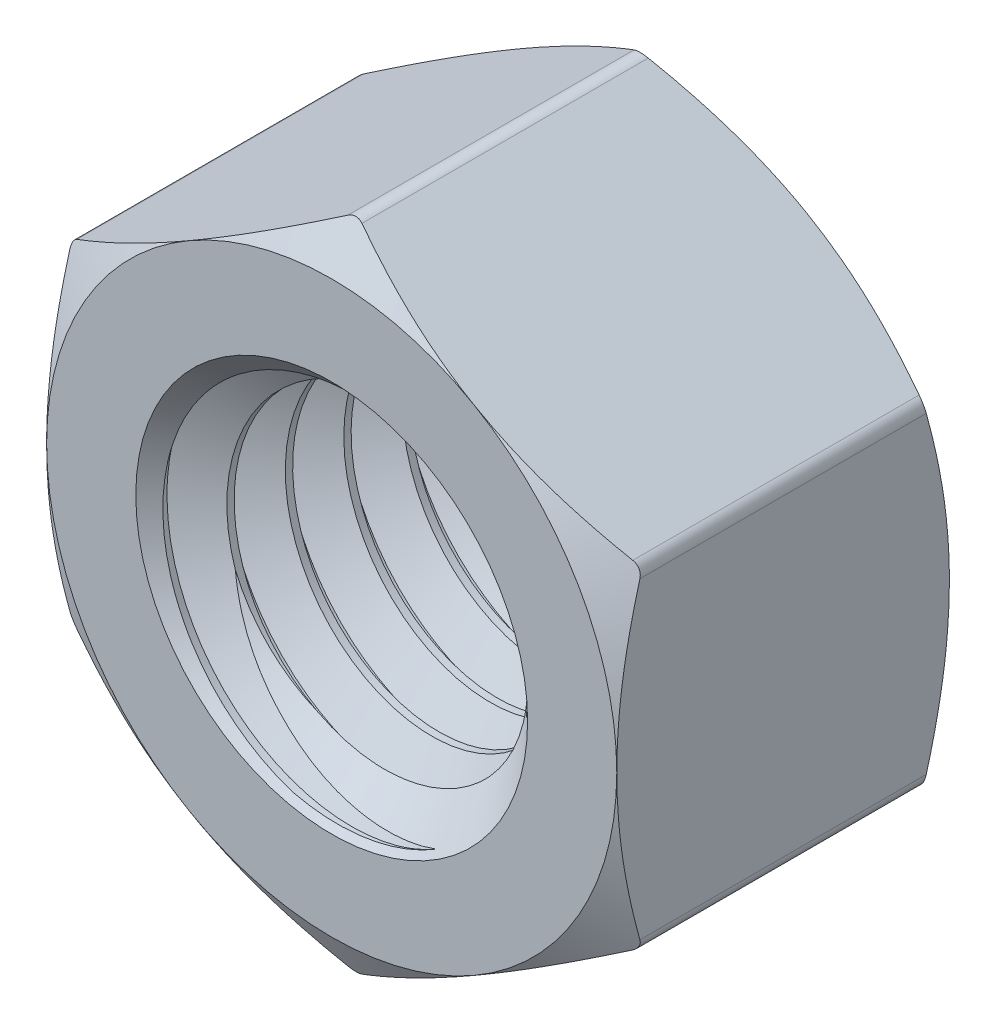
SolidWorks part; units mm, degrees
ref_plane "Front" through (0, 0, 0) normal (0, 0, 1) x (1, 0, 0)
ref_plane "Top" through (0, 0, 0) normal (0, 1, 0) x (1, 0, 0)
ref_plane "Right" through (0, 0, 0) normal (1, 0, 0) x (0, 0, -1)
sketch "Sketch1" plane through (0, 0, 0) normal (0, 0, 1) x (1, 0, 0)
  line L0 (0, 6.35) -> (0, 4.3962) construction
  line L1 (-9.525, 5.4993) -> (-9.525, -5.4993)
  line L2 (-9.525, -5.4993) -> (0, -10.9985)
  line L3 (0, -10.9985) -> (9.525, -5.4993)
  line L4 (9.525, -5.4993) -> (9.525, 5.4993)
  line L5 (9.525, 5.4993) -> (0, 10.9985)
  line L6 (0, 10.9985) -> (-9.525, 5.4993)
  circle A0 centre (0, 0) radius 9.525 construction
  circle A1 centre (0, 0) radius 6.35 construction
  point P10 (0, 6.35)
  dimension "Width" = 19.05
  dimension "Thread Size" = 12.7
  dimension "Thread Pitch" = 1.9538
sketch "Sketch2" plane through (0, 0, 0) normal (1, 0, 0) x (0, 0, -1)
  line L0 (-5.5562, 0) -> (5.5562, 0) construction
  line L1 (-5.5562, 10.9985) -> (5.5562, 10.9985) construction
  dimension "Height" = 11.1125
sketch "Sketch15" plane through (0, 0, 0) normal (0, 0, 1) x (1, 0, 0)
  line L1 (0, 10.9985) -> (-9.525, 5.4993)
  line L2 (-9.525, 5.4993) -> (-9.525, -5.4993)
  line L3 (-9.525, -5.4993) -> (0, -10.9985)
  line L4 (0, -10.9985) -> (9.525, -5.4993)
  line L5 (9.525, -5.4993) -> (9.525, 5.4993)
  line L6 (9.525, 5.4993) -> (0, 10.9985)
  circle A0 centre (0, 0) radius 9.525 construction
extrude "Boss-Extrude2" add sketch "Sketch15" along normal mid plane 11.1125
sketch "Sketch16" plane through (0, 0, 0) normal (0, 0, 1) x (1, 0, 0)
  circle A0 centre (0, 0) radius 6.35 construction
  circle A1 centre (0, 0) radius 6.35
sketch "Sketch4" plane through (0, 0, -5.5562) normal (0, 0, -1) x (-1, 0, 0)
  circle A0 centre (0, 0) radius 6.35 construction
  circle A1 centre (0, 0) radius 6.35
extrude "Cut-Extrude4" cut sketch "Sketch16" against normal through all both and the other way through all
sketch "Sketch7" plane through (0, 0, 5.5562) normal (0, 0, 1) x (1, 0, 0)
  circle A0 centre (0, 0) radius 9.525 construction
  circle A1 centre (0, 0) radius 9.525
extrude "Cut-Extrude5" cut sketch "Sketch7" against normal through all draft 60 flip side to cut
mirror "Mirror4" about plane through (0, 0, 0) normal (0, 0, 1) of "Cut-Extrude5"
fillet "Fillet2" radius 0.4763 6 edges at (-9.525, 5.4993, 0) (-9.525, -5.4993, 0) (0, -10.9985, 0) (9.525, -5.4993, 0) (9.525, 5.4993, 0) (0, 10.9985, 0)
sketch "Sketch8" plane through (0, 0, 5.5562) normal (0, 0, 1) x (1, 0, 0)
  line L0 (1.6435, -6.1336) -> (0, 0) construction
  line L2 (0, 6.35) -> (0, 4.3962) construction
  circle A0 centre (0, 0) radius 6.35 construction
  point P0 (1.6435, -6.1336)
  dimension "D1" = 15
sketch "Sketch13" plane through (0, 0, -5.5562) normal (0, 0, -1) x (-1, 0, 0)
  circle A0 centre (0, 0) radius 6.35 construction
  circle A1 centre (0, 0) radius 6.35
extrude "Boss-Extrude1" add sketch "Sketch13" against normal up to surface (11.1125 mm away) separate body up to face at (6.35, 0, 5.5562)
curve "Helix/Spiral3" pitch 1.9538 height 13.0663 radius 6.35 centre (0, 0, -5.5562) axis (0, 0, 1) start towards (0, 1, 0)
sketch "Sketch12" plane through (0, 0, 0) normal (1, 0, 0) x (0, 0, -1)
  line L0 (7.2659, 6.35) -> (5.5562, 6.35)
  line L1 (7.2659, 6.35) -> (6.5332, 5.0809)
  line L2 (6.5332, 5.0809) -> (6.2889, 5.0809)
  line L3 (6.2889, 5.0809) -> (5.5562, 6.35)
  line L4 (6.4111, 5.0809) -> (6.4111, 6.35) construction
  line L5 (5.9226, 5.7155) -> (6.8995, 5.7155) construction
  dimension "D1" = 60
  dimension "D2" = 0.2442
  dimension "D3" = 0.9769
sweep "Cut-Sweep1" cut profiles "Sketch12" path "Helix/Spiral3" align with end faces yes
sketch "Sketch17" plane through (0, 0, 5.5562) normal (0, 0, 1) x (1, 0, 0)
  circle A1 centre (0, 0) radius 6.35
  circle A2 centre (0, 0) radius 6.35
  dimension "D1" = 0
extrude "Boss-Extrude3" add sketch "Sketch17" against normal up to surface (11.1125 mm away) up to face at (6.35, 0, -5.5562)
combine bodies "Combine1" operation type subtract main body 127 bodies to subtract 118
sketch "Sketch10" plane through (0, 0, 5.5562) normal (0, 0, 1) x (1, 0, 0)
  circle A0 centre (0, 0) radius 6.35 construction
  circle A1 centre (0, 0) radius 6.35 construction
  circle A2 centre (0, 0) radius 6.5454
  dimension "D1" = 0.1954
extrude "Cut-Extrude2" cut sketch "Sketch10" against normal through all draft 45
sketch "Sketch11" plane through (0, 0, -5.5562) normal (0, 0, -1) x (-1, 0, 0)
  circle A1 centre (0, 0) radius 6.5454 construction
  circle A2 centre (0, 0) radius 6.5454
extrude "Cut-Extrude3" cut sketch "Sketch11" against normal through all draft 45
equation "\"D1\"= \"Height@Sketch2\""
equation "\"D3@Helix/Spiral3\"=\"Height@Sketch2\"+\"Thread Pitch@Sketch1\""
equation "\"D4@Helix/Spiral3\"=\"Thread Pitch@Sketch1\""
equation "\"D2@Sketch12\" = \"D4@Helix/Spiral3\"*.125"
equation "\"D3@Sketch12\" = \"D4@Helix/Spiral3\"*.50"
equation "\"D1@Boss-Extrude2\"=\"Height@Sketch2\""
equation "\"D1@Fillet2\"=\"Width@Sketch1\"*0.025"
equation "\"D1@Sketch10\"=\"Thread Pitch@Sketch1\"*0.1"
